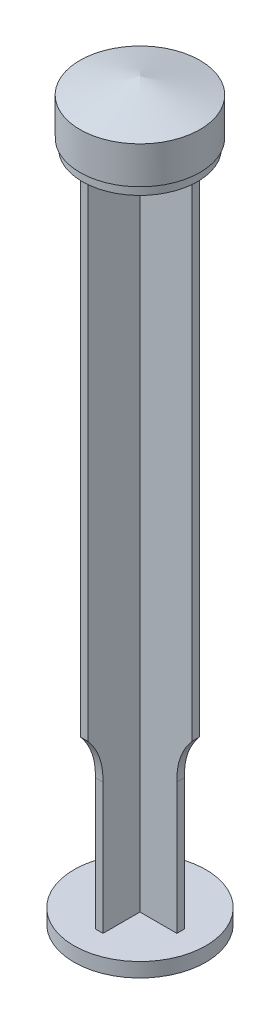
SolidWorks part; units mm, degrees
ref_plane "Front Plane" through (0, 0, 0) normal (0, 0, 1) x (1, 0, 0)
ref_plane "Top Plane" through (0, 0, 0) normal (0, 1, 0) x (1, 0, 0)
ref_plane "Right Plane" through (0, 0, 0) normal (1, 0, 0) x (0, 0, -1)
ref_axis "Axis1" through (-33.0333, 0, 0) along (1, 0, 0)
ref_axis "Axis2" through (0, 24.5224, 0) along (0, -1, 0)
ref_axis "Axis3" through (0, 0, -52.9538) along (0, 0, 1)
sketch "Sketch1" plane through (0, 0, 0) normal (0, 1, 0) x (1, 0, 0)
  circle A0 centre (0, 0) radius 8.3
  dimension "D1" = 16.6
extrude "Boss-Extrude1" add sketch "Sketch1" along normal blind 1.8
sketch "Sketch2" plane through (0, 1.8, 0) normal (0, 1, 0) x (1, 0, 0)
  line L0 (-0.475, 0.475) -> (-0.475, 7)
  line L1 (-0.475, 7) -> (0.475, 7)
  line L2 (0.475, 7) -> (0.475, 0.475)
  line L3 (0.475, 0.475) -> (7, 0.475)
  line L4 (7, 0.475) -> (7, -0.475)
  line L5 (7, -0.475) -> (0.475, -0.475)
  line L6 (0.475, -0.475) -> (0.475, -7)
  line L7 (0.475, -7) -> (-0.475, -7)
  line L8 (-0.475, -7) -> (-0.475, -0.475)
  line L9 (-0.475, -0.475) -> (-7, -0.475)
  line L10 (-7, -0.475) -> (-7, 0.475)
  line L11 (-7, 0.475) -> (-0.475, 0.475)
  line L12 (-0.475, 0.475) -> (0.475, -0.475) construction
  line L13 (-0.475, -0.475) -> (0.475, 0.475) construction
  point P2 (0, 0)
  dimension "D1" = 0.95
  dimension "D2" = 14
extrude "Boss-Extrude2" add sketch "Sketch2" along normal blind 82.75
sketch "Sketch3" plane through (0, 84.55, 0) normal (0, 1, 0) x (1, 0, 0)
  circle A0 centre (0, 0) radius 7.25
  dimension "D1" = 14.5
extrude "Boss-Extrude3" add sketch "Sketch3" along normal blind 1.15
sketch "Sketch4" plane through (0, 85.7, 0) normal (0, 1, 0) x (1, 0, 0)
  circle A0 centre (0, 0) radius 7.55
  dimension "D1" = 15.1
extrude "Boss-Extrude4" add sketch "Sketch4" along normal blind 6.7
chamfer "Chamfer1" distance 2.023 angle 75 1 edges at (0, 92.4, 7.55) first distance on face at (0, 92.4, 7.55)
sketch "Sketch7" plane through (0.475, 0, 0) normal (1, 0, 0) x (0, 0, -1)
  line L0 (-7, 1.8) -> (-7, 23.65)
  line L1 (-7, 84.55) -> (-7, 1.8) construction
  line L2 (-7, 1.8) -> (-5.125, 1.8)
  line L3 (8.3, 1.8) -> (-8.3, 1.8) construction
  line L4 (-5.125, 1.8) -> (-5.125, 18.3)
  line L5 (0, 14.1454) -> (0, -14.1454) construction
  line L6 (5.125, 1.8) -> (5.125, 18.3)
  line L7 (7, 1.8) -> (5.125, 1.8)
  line L8 (7, 1.8) -> (7, 23.65)
  spline S0 degree 2 poles (-5.125, 18.3) (-5.0595, 21.3387) (-7, 23.65) knots 0 0 0 1 1 1
  spline S1 degree 2 poles (5.125, 18.3) (5.0595, 21.3387) (7, 23.65) knots 0 0 0 1 1 1
  point P17 (5.3293, 21.135)
  point P19 (-5.6166, 21.3101)
  dimension "D1" = 16.5
  dimension "D2" = 21.85
  dimension "D3" = 5.125
extrude "Cut-Extrude1" cut sketch "Sketch7" against normal blind 2 and the other way blind 2
sketch "Sketch8" plane through (0, 0, 0) normal (0, 0, 1) x (1, 0, 0)
  line L0 (-7, 1.8) -> (-7, 23.65)
  line L1 (-7, 1.8) -> (-5.125, 1.8)
  line L2 (-5.125, 1.8) -> (-5.125, 18.3)
  line L6 (8.3, 1.8) -> (-8.3, 1.8) construction
  line L7 (-7, 84.55) -> (-7, 1.8) construction
  line L8 (0, -13.0494) -> (0, 13.0494) construction
  line L9 (7, 1.8) -> (5.125, 1.8)
  line L10 (5.125, 1.8) -> (5.125, 18.3)
  line L11 (7, 1.8) -> (7, 23.65)
  spline S0 degree 2 poles (-5.125, 18.3) (-5.0284, 21.3459) (-7, 23.65) knots 0 0 0 1 1 1
  spline S1 degree 2 poles (5.125, 18.3) (5.0284, 21.3459) (7, 23.65) knots 0 0 0 1 1 1
  point P5 (0, 0)
  point P6 (-5.5814, 21.2607)
  point P10 (-7, 1.8)
  point P12 (-4.6453, 1.8)
  point P15 (-7, 23.65)
  dimension "D3" = 5.125
  dimension "D1" = 21.85
  dimension "D2" = 16.5
extrude "Cut-Extrude2" cut sketch "Sketch8" against normal blind 2 and the other way blind 2
